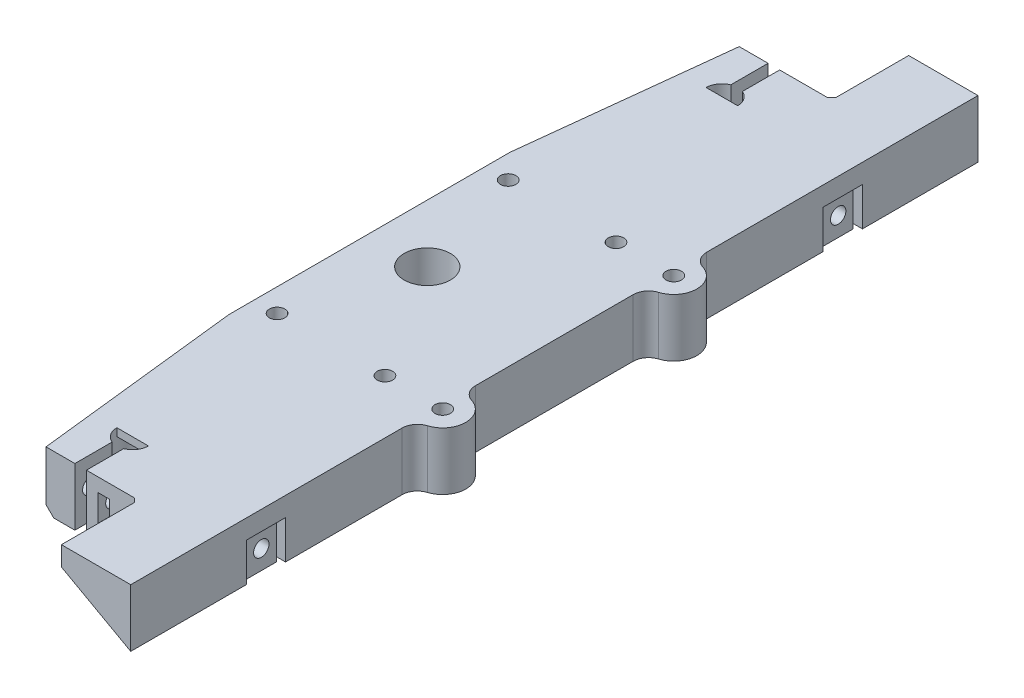
SolidWorks part; units mm, degrees
material "ABS"
ref_plane "Płaszczyzna przednia" through (0, 0, 0) normal (0, 0, 1) x (1, 0, 0)
ref_plane "Płaszczyzna górna" through (0, 0, 0) normal (0, 1, 0) x (1, 0, 0)
ref_plane "Płaszczyzna prawa" through (0, 0, 0) normal (1, 0, 0) x (0, 0, -1)
sketch "Szkic1" plane through (0, 0, 0) normal (0, 1, 0) x (1, 0, 0)
  line L0 (-20.5, 36.5) -> (-14.5, 90)
  line L1 (27.5, -90) -> (-14.5, -90)
  line L2 (27.5, -90) -> (27.5, 90)
  line L3 (27.5, 90) -> (-14.5, 90)
  line L4 (-20.5, -36.5) -> (-20.5, 36.5)
  line L5 (27.5, 0) -> (-46.9742, 0) construction
  line L6 (-7, -80.3158) -> (-7, -90)
  line L7 (-20.5, -36.5) -> (-14.5, -90)
  line L8 (-4, -80.3158) -> (-4, -90)
  line L9 (-7, 80.3158) -> (-7, 90)
  line L10 (-4, 80.3158) -> (-4, 90)
  circle A0 centre (-14.5, 30) radius 2
  circle A1 centre (13.5, 30) radius 2
  circle A4 centre (13.5, -30) radius 2
  circle A5 centre (-14.5, -30) radius 2
  circle A6 centre (-5.5, -76.5) radius 4.1
  circle A7 centre (-5.5, 0) radius 6
  circle A8 centre (-5.5, 76.5) radius 4.1
  point P0 (0, 0)
  dimension "D7" = 6
  dimension "D10" = 4
  dimension "D11" = 30
  dimension "D12" = 15
  dimension "D13" = 12
  dimension "D16" = 8.2
  dimension "D1" = 48
  dimension "D2" = 180
  dimension "D3" = 27.5
  dimension "D4" = 90
  dimension "D5" = 42
  dimension "D6" = 73
  dimension "D8" = 28
  dimension "D14" = 13.5
  dimension "D15" = 15
  dimension "D17" = 3
  dimension "D19" = 13.5
  dimension "D20" = 3
extrude "Dodanie-wyciągnięcie1" add sketch "Szkic1" along normal blind 15 contours L2 L5 A7 L4 L7 L1 L6 A6 L8 A5 A4 | L5 L2 L3 L10 A8 L9 L0 L4 A7 A0 A1 region at (4.7191, 0, -43.9009) region at (4.7191, 0, 43.9009)
sketch "Szkic3" plane through (0, 15, 0) normal (0, 1, 0) x (1, 0, 0)
  line L0 (-9.6, 76.5) -> (-1.4, 76.5)
  line L1 (-9.6, -76.5) -> (-1.4, -76.5)
  arc A0 (-7, 80.3158) -> (-4, 80.3158) centre (-5.5, 76.5) ccw construction
  arc A1 (-4, -80.3158) -> (-7, -80.3158) centre (-5.5, -76.5) ccw construction
  arc A2 (-7, 80.3158) -> (-4, 80.3158) centre (-5.5, 76.5) ccw
  arc A3 (-4, -80.3158) -> (-7, -80.3158) centre (-5.5, -76.5) ccw
  arc M7 (-4, 80.3158) -> (-7, 80.3158) centre (-5.5, 76.5) cw
  arc M15 (-7, -80.3158) -> (-4, -80.3158) centre (-5.5, -76.5) cw
extrude "Dodanie-wyciągnięcie3" add sketch "Szkic3" against normal blind 2 contours L1 M15 | L0 M7 region at (-5.5, 15, -74.7599) region at (-5.5, 15, 74.7599)
sketch "Szkic4" plane through (0, 15, 0) normal (0, 1, 0) x (1, 0, 0)
  circle A0 centre (28.5, -30) radius 2
  circle A1 centre (28.5, 30) radius 2
  circle A2 centre (13.5, 30) radius 2 construction
  circle A3 centre (13.5, -30) radius 2 construction
  circle A4 centre (13.5, 30) radius 2
  circle A5 centre (13.5, -30) radius 2
  circle A6 centre (28.5, -30) radius 6
  circle A7 centre (28.5, 30) radius 6
  line M4 (27.5, -90) -> (27.5, 90)
  dimension "D1" = 4
  dimension "D2" = 4
  dimension "D4" = 12
  dimension "D5" = 12
  dimension "D3" = 15
extrude "Dodanie-wyciągnięcie4" add sketch "Szkic4" against normal blind 15 contours A6 A0 M4 | A7 A1 M4 region at (30.8051, 15, 30) region at (30.8051, 15, -30)
sketch "Szkic5" plane through (0, 15, 0) normal (0, 1, 0) x (1, 0, 0)
  line L16 (27.5, -90) -> (27.5, -35.9161)
  line L17 (27.5, -24.0839) -> (27.5, 24.0839)
  line L18 (27.5, 35.9161) -> (27.5, 90)
  line L19 (27.5, 90) -> (-4, 90)
  line L20 (-4, 90) -> (-4, 80.3158)
  line L21 (-1.4, 76.5) -> (-9.6, 76.5)
  line L22 (-7, 80.3158) -> (-7, 90)
  line L23 (-7, 90) -> (-14.5, 90)
  line L24 (-14.5, 90) -> (-20.5, 36.5)
  line L25 (-20.5, 36.5) -> (-20.5, -36.5)
  line L26 (-20.5, -36.5) -> (-14.5, -90)
  line L27 (-14.5, -90) -> (-7, -90)
  line L28 (-7, -90) -> (-7, -80.3158)
  line L29 (-9.6, -76.5) -> (-1.4, -76.5)
  line L30 (-4, -80.3158) -> (-4, -90)
  line L31 (-4, -90) -> (27.5, -90)
  line L32 (27.5, -90) -> (27.5, -35.9161)
  line L33 (27.5, -24.0839) -> (27.5, 24.0839)
  line L34 (27.5, 35.9161) -> (27.5, 90)
  line L35 (27.5, 90) -> (-4, 90)
  line L36 (-4, 90) -> (-4, 80.3158)
  line L37 (-1.4, 76.5) -> (-9.6, 76.5)
  line L38 (-7, 80.3158) -> (-7, 90)
  line L39 (-7, 90) -> (-14.5, 90)
  line L40 (-14.5, 90) -> (-20.5, 36.5)
  line L41 (-20.5, 36.5) -> (-20.5, -36.5)
  line L42 (-20.5, -36.5) -> (-14.5, -90)
  line L43 (-14.5, -90) -> (-7, -90)
  line L44 (-7, -90) -> (-7, -80.3158)
  line L45 (-9.6, -76.5) -> (-1.4, -76.5)
  line L46 (-4, -80.3158) -> (-4, -90)
  line L47 (-4, -90) -> (27.5, -90)
  arc A0 (27.5, 28.2679) -> (27.5, 31.7321) centre (28.5, 30) ccw construction
  arc A1 (27.5, 28.2679) -> (27.5, 31.7321) centre (28.5, 30) ccw
  arc A2 (27.5, -31.7321) -> (27.5, -28.2679) centre (28.5, -30) ccw construction
  arc A3 (27.5, -31.7321) -> (27.5, -28.2679) centre (28.5, -30) ccw
  circle A4 centre (28.5, 30) radius 2
  circle A5 centre (28.5, -30) radius 2
  arc A6 (27.5, -35.9161) -> (27.5, -24.0839) centre (28.5, -30) ccw
  arc A7 (27.5, 24.0839) -> (27.5, 35.9161) centre (28.5, 30) ccw
  arc A8 (-1.4, 76.5) -> (-4, 80.3158) centre (-5.5, 76.5) ccw
  arc A9 (-7, 80.3158) -> (-9.6, 76.5) centre (-5.5, 76.5) ccw
  arc A10 (-9.6, -76.5) -> (-7, -80.3158) centre (-5.5, -76.5) ccw
  arc A11 (-4, -80.3158) -> (-1.4, -76.5) centre (-5.5, -76.5) ccw
  arc A12 (27.5, -35.9161) -> (27.5, -24.0839) centre (28.5, -30) ccw
  arc A13 (27.5, 24.0839) -> (27.5, 35.9161) centre (28.5, 30) ccw
  arc A14 (-1.4, 76.5) -> (-4, 80.3158) centre (-5.5, 76.5) ccw
  arc A15 (-7, 80.3158) -> (-9.6, 76.5) centre (-5.5, 76.5) ccw
  arc A16 (-9.6, -76.5) -> (-7, -80.3158) centre (-5.5, -76.5) ccw
  arc A17 (-4, -80.3158) -> (-1.4, -76.5) centre (-5.5, -76.5) ccw
  arc M23 (27.5, 31.7321) -> (27.5, 28.2679) centre (28.5, 30) cw
  line M24 (27.5, 28.2679) -> (27.5, 31.7321)
  arc M25 (27.5, -28.2679) -> (27.5, -31.7321) centre (28.5, -30) cw
  line M26 (27.5, -31.7321) -> (27.5, -28.2679)
  dimension "D2" = 4
  dimension "D3" = 4
  dimension "D1" = 0
extrude "Wytnij-wyciągnięcie1" cut sketch "Szkic5" against normal blind 15 contours M25 M26 | A5 M26 | A4 M24 | M23 M24 region at (28.8427, 15, -30) region at (27.09, 15, -30) region at (28.8427, 15, 30) region at (27.09, 15, 30)
fillet "Zaokrąglenie1" radius 4 4 edges at (27.5, 7.5, -35.9161) (27.5, 7.5, -24.0839) (27.5, 7.5, 24.0839) (27.5, 7.5, 35.9161)
chamfer "Sfazowanie1" distance 2 angle 45 3 edges at (-17.5, 0, -63.25) (-17.5, 0, 63.25) (-20.5, 0, 0)
sketch "Szkic8" plane through (-4, 0, 0) normal (-1, 0, 0) x (0, 0, 1)
  line L0 (90, 15) -> (90, 0) construction
  line L1 (80.3158, 15) -> (90, 15) construction
  circle A0 centre (86, 8) radius 2
  dimension "D1" = 4
  dimension "D2" = 4
  dimension "D3" = 7
extrude "Wytnij-wyciągnięcie3" cut sketch "Szkic8" along normal through all and the other way blind 7
sketch "Szkic9" plane through (-4, 0, 0) normal (-1, 0, 0) x (0, 0, 1)
  circle A0 centre (86, 8) radius 3.5
  dimension "D1" = 7
extrude "Wytnij-wyciągnięcie4" cut sketch "Szkic9" along normal blind 4 from offset 8
sketch "Szkic10" plane through (-4, 0, 0) normal (-1, 0, 0) x (0, 0, 1)
  line L0 (86, 11.4641) -> (90, 11.4641)
  line L1 (86, 11.4641) -> (83, 9.7321)
  line L2 (83, 9.7321) -> (83, 6.2679)
  line L3 (83, 6.2679) -> (86, 4.5359)
  line L4 (86, 4.5359) -> (89, 6.2679)
  line L5 (89, 6.2679) -> (89, 9.7321)
  line L6 (89, 9.7321) -> (86, 11.4641)
  line L7 (90, 15) -> (90, 0) construction
  line L8 (90, 11.4641) -> (90, 4.5359)
  line L9 (90, 4.5359) -> (86, 4.5359)
  circle A0 centre (86, 8) radius 3 construction
  circle M1 centre (86, 8) radius 2
  line M3 (90, 0) -> (90, 15)
  dimension "D1" = 6
extrude "Wytnij-wyciągnięcie5" cut sketch "Szkic10" against normal blind 3 from offset 3 contours L5 L6 L1 L2 L3 L4 M1 | L9 L0 L6 L5 L4 M3 region at (-4, 10.5187, 87.4542) region at (-4, 11.3841, 88) offset against normal yes
mirror "Lustro2" about plane through (0, 0, 0) normal (0, 0, 1) of "Wytnij-wyciągnięcie5", "Wytnij-wyciągnięcie4", "Wytnij-wyciągnięcie3"
sketch "Szkic12" plane through (0, 0, 0) normal (0, -1, 0) x (1, 0, 0)
  line L0 (27.5, 90) -> (-4, 90) construction
  line L1 (27.5, 80) -> (17.3, 80)
  line L2 (27.5, 80) -> (27.5, 69.8)
  line L3 (27.5, 69.8) -> (17.3, 69.8)
  line L4 (17.3, 80) -> (17.3, 69.8)
  line L5 (27.5, 80) -> (17.3, 69.8) construction
  line L6 (27.5, 69.8) -> (17.3, 80) construction
  line L7 (27.5, 90) -> (27.5, 39.5394) construction
  line L8 (27.5, -39.5394) -> (27.5, -90) construction
  line L9 (18.5, 78.8) -> (26.3, 78.8)
  line L10 (18.5, 78.8) -> (18.5, 71)
  line L11 (18.5, 71) -> (26.3, 71)
  line L12 (26.3, 78.8) -> (26.3, 71)
  line L13 (18.5, 78.8) -> (26.3, 71) construction
  line L14 (18.5, 71) -> (26.3, 78.8) construction
  line L15 (27.5, -69.8) -> (17.3, -69.8)
  line L16 (27.5, -69.8) -> (27.5, -80)
  line L17 (27.5, -80) -> (17.3, -80)
  line L18 (17.3, -69.8) -> (17.3, -80)
  line L19 (27.5, -69.8) -> (17.3, -80) construction
  line L20 (27.5, -80) -> (17.3, -69.8) construction
  line L21 (27.5, -90) -> (-4, -90) construction
  line L23 (18.5, -71) -> (26.3, -71)
  line L24 (18.5, -71) -> (18.5, -78.8)
  line L25 (18.5, -78.8) -> (26.3, -78.8)
  line L26 (26.3, -71) -> (26.3, -78.8)
  line L27 (18.5, -71) -> (26.3, -78.8) construction
  line L28 (18.5, -78.8) -> (26.3, -71) construction
  point P0 (22.4, 74.9)
  point P5 (22.4, -74.9)
  point P11 (22.4, 74.9)
  point P23 (22.4, -74.9)
  line M14 (27.5, -90) -> (27.5, -39.5394)
  line M22 (27.5, 39.5394) -> (27.5, 90)
  dimension "D1" = 10.2
  dimension "D2" = 20.2
  dimension "D3" = 7.8
  dimension "D4" = 10.2
  dimension "D5" = 20.2
  dimension "D6" = 7.8
extrude "Wytnij-wyciągnięcie7" cut sketch "Szkic12" against normal blind 10 contours L1 L4 L3 L9 L12 L11 L10 M22 | L15 L18 L17 L23 L26 L25 L24 M14 region at (27.3558, 0, 74.9) region at (27.3558, 0, -74.9)
sketch "Szkic13" plane through (26.3, 0, 0) normal (1, 0, 0) x (0, 0, -1)
  line L0 (78.8, 10) -> (78.8, 0) construction
  line L2 (80, 10) -> (69.8, 10) construction
  line L3 (-71, 10) -> (-71, 0) construction
  circle A0 centre (74.9, 5) radius 2
  circle A1 centre (-74.9, 5) radius 2
  dimension "D1" = 3.9
  dimension "D3" = 4
  dimension "D4" = 3.9
  dimension "D2" = 5
extrude "Wytnij-wyciągnięcie8" cut sketch "Szkic13" against normal blind 8
sketch "Szkic14" plane through (0, 0, -90) normal (0, 0, -1) x (-1, 0, 0)
  line L0 (-27.5, 0) -> (-27.5, 15)
  line L1 (-27.5, 0) -> (4, 0) construction
  line L2 (-27.5, 15) -> (4, 15) construction
  line L3 (-27.5, 15) -> (-0.4393, 15)
  line L4 (-0.4393, 15) -> (-27.5, 0)
  line L5 (-27.5, 15) -> (-27.5, 0) construction
  line L6 (-9.5, 9.9776) -> (-9.5, 15)
  line M6 (-27.5, 15) -> (-27.5, 0)
  dimension "D1" = 61
  dimension "D2" = 18
extrude "Dodanie-wyciągnięcie5" add sketch "Szkic14" along normal blind 20 contours L4 L6 L3 M6 region at (19.995, 9.5801, -90)
sketch "Szkic15" plane through (6.4636, 11.6607, 0) normal (-0.4848, -0.8746, 0) x (0.8746, -0.4848, 0)
  line L0 (24.052, -90) -> (-3.4985, -90) construction
  line L1 (3.4717, -110) -> (3.4717, -90) construction
  circle A0 centre (13.3717, -100) radius 5.1
  dimension "D1" = 10
  dimension "D3" = 10.2
  dimension "D2" = 9.9
extrude "Wytnij-wyciągnięcie9" cut sketch "Szkic15" against normal blind 7
mirror "Lustro4" about plane through (0, 0, 0) normal (0, 0, 1) of "Dodanie-wyciągnięcie5", "Wytnij-wyciągnięcie9"
chamfer "Sfazowanie2" distance 1 angle 45 4 edges at (9.5, 12.4888, -90) (18.5, 4.9888, -90) (9.5, 12.4888, 90) (18.5, 4.9888, 90)
